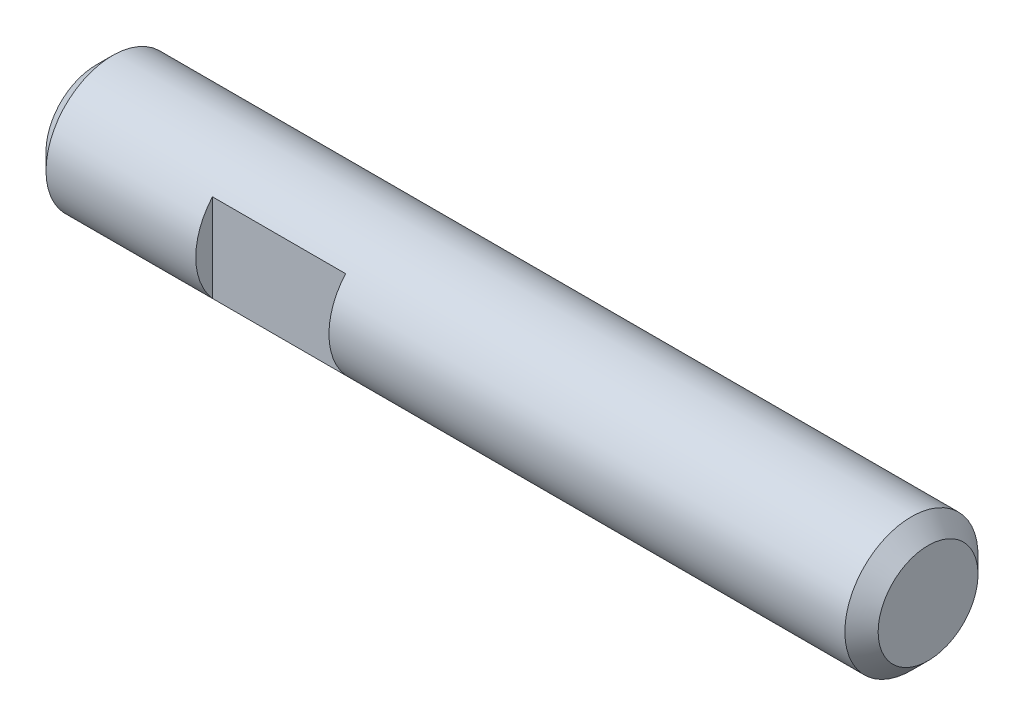
SolidWorks part; units mm, degrees
material "1.4301 (X5CrNi18-10)"
ref_plane "Plan de face" through (0, 0, 0) normal (0, 0, 1) x (1, 0, 0)
ref_plane "Plan de dessus" through (0, 0, 0) normal (0, 1, 0) x (1, 0, 0)
ref_plane "Plan de droite" through (0, 0, 0) normal (1, 0, 0) x (0, 0, -1)
ref_plane "Plan1" through (0, 0, 0) normal (0, 0, 1) x (1, 0, 0)
sketch "Esquisse1" plane through (0, 0, 0) normal (0, 0, 1) x (1, 0, 0)
  line L0 (0, 0) -> (0, 1.5)
  line L1 (0, 1.5) -> (0.5, 2)
  line L2 (0.5, 2) -> (24.5, 2)
  line L3 (24.5, 2) -> (25, 1.5)
  line L4 (25, 1.5) -> (25, 0)
  line L5 (25, 0) -> (0, 0)
  line L6 (25, 0) -> (0, 0) construction
revolve "Révolution1" add sketch "Esquisse1" angle 360 about L6 reverse direction yes
ref_plane "Plan2" through (0, 0, 0) normal (0, 1, 0) x (1, 0, 0)
sketch "Esquisse2" plane through (0, 0, 0) normal (0, 1, 0) x (1, 0, 0)
  line L0 (5, -1.5) -> (5, -2)
  line L1 (5, -2) -> (9, -2)
  line L2 (9, -2) -> (9, -1.5)
  line L3 (9, -1.5) -> (5, -1.5)
extrude "Enlèv. mat.-Extru.1" cut sketch "Esquisse2" against normal blind 4 and the other way blind 4
